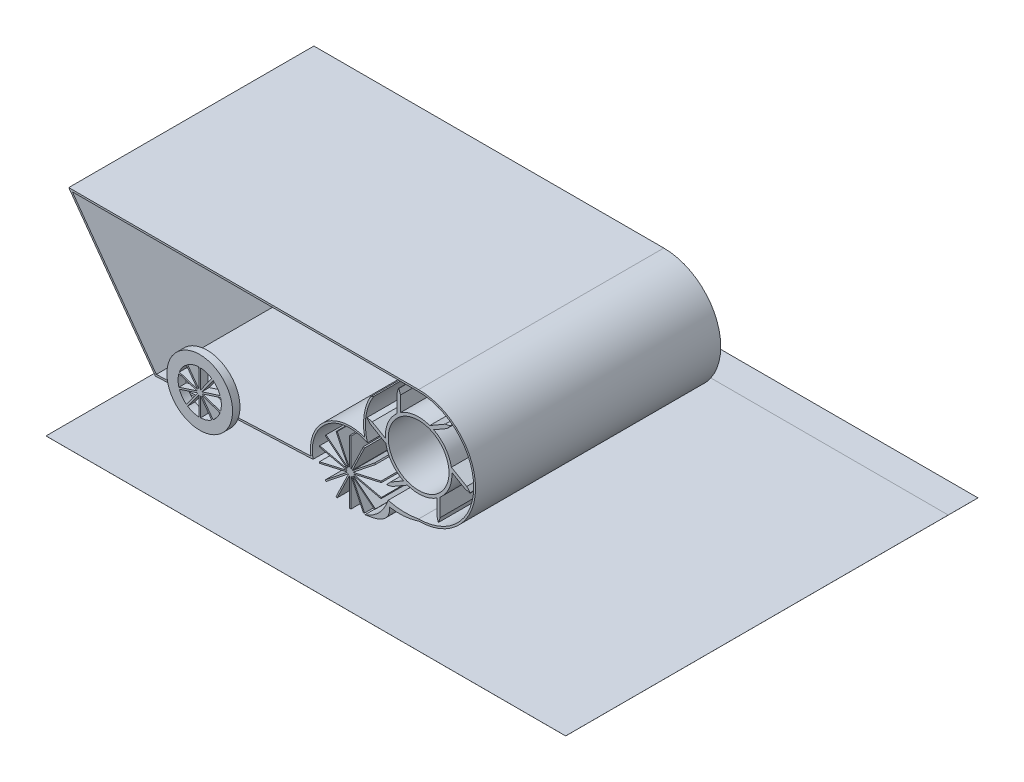
SolidWorks part; units mm, degrees
ref_plane "Front Plane" through (0, 0, 0) normal (0, 0, 1) x (1, 0, 0)
ref_plane "Top Plane" through (0, 0, 0) normal (0, 1, 0) x (1, 0, 0)
ref_plane "Right Plane" through (0, 0, 0) normal (1, 0, 0) x (0, 0, -1)
sketch "Sketch1" plane through (0, 0, 0) normal (0, 0, 1) x (1, 0, 0)
  line L0 (-32.4096, 6.9538) -> (-74.0166, 5.1847)
  line L1 (-79.7094, 0) -> (60.1844, 0)
  line L2 (-79.7094, 0) -> (-79.7094, -0.01)
  line L3 (-79.7094, -0.01) -> (60.1844, -0.01)
  line L4 (60.1844, 0) -> (60.1844, -0.01)
  line L5 (-74.0166, 5.1847) -> (-96.613, 36.459)
  line L6 (-96.613, 36.459) -> (-3.402, 36.459)
  line L7 (-17.8302, 0.5667) -> (-11.617, 7.0387) construction
  line L8 (-17.4695, 0.2204) -> (-11.4099, 6.5323) construction
  line L9 (-31.8198, 6.4784) -> (-74.2642, 4.6737)
  line L10 (-74.2642, 4.6737) -> (-97.5911, 36.959)
  line L11 (-97.5911, 36.959) -> (-3.402, 36.959)
  line L12 (-16.3995, 28.7718) -> (-15.5246, 29.2718)
  line L13 (-11.617, 7.0387) -> (-3.402, 6.7959) construction
  line L14 (-16.3995, 28.7718) -> (-64.1017, 28.7718) construction
  line L15 (-15.5246, 29.2718) -> (-64.1017, 29.2718) construction
  line L16 (-11.4099, 6.5323) -> (-3.4095, 6.2959) construction
  circle A0 centre (-21.7751, 8.5048) radius 8.5048
  circle A1 centre (-3.402, 21.6275) radius 14
  arc A2 (-3.402, 6.7959) -> (-3.402, 36.459) centre (-3.402, 21.6275) ccw
  arc A3 (-17.9069, 18.5316) -> (-32.4096, 6.9538) centre (-21.7751, 8.5048) ccw
  arc A4 (-16.3995, 28.7718) -> (-17.9069, 18.5316) centre (-3.402, 21.6275) ccw
  arc A5 (-15.5246, 29.2718) -> (-17.1737, 17.6606) centre (-3.402, 21.6275) ccw
  arc A6 (-17.1737, 17.6606) -> (-31.8198, 6.4784) centre (-21.7751, 8.5048) ccw
  arc A7 (-3.4095, 6.2959) -> (-3.402, 36.959) centre (-3.402, 21.6275) ccw
  spline S0 degree 2 poles (-17.8302, 0.5667) (-13.2891, 2.1793) (-11.617, 7.0387) knots 0 0 0 1 1 1
  spline S1 degree 2 poles (-11.617, 7.0387) (-7.5737, 5.9985) (-3.402, 6.7959) knots 0 0 0 1 1 1
  spline S2 degree 2 poles (-11.2502, 5.6568) (-7.3029, 4.9959) (-3.4095, 6.2959) knots 0 0 0 1 1 1
  spline S3 degree 3 poles (-17.8302, 0.5667) (-13.1441, 1.0958) (-10.9508, 2.7924) (-11.2502, 5.6568) knots 0 0 0 0 0.910766 0.910766 0.910766 0.910766
  point P15 (-32.4096, 6.9538)
  dimension "D2" = 28
  dimension "D1" = 0.5
extrude "Boss-Extrude1" add sketch "Sketch1" along normal blind 65 contours S0 S3 S2 A7 L11 L10 L9 A6 A5 L12 A4 A3 L0 L5 L6 A2 S1 | A0 | A1 | L1 L4 L3 L2 region at (-28.4081, 16.8136, 0) region at (-21.7751, 8.5048, 0) region at (-3.402, 21.6275, 0)
sketch "Sketch2" plane through (0, 0, 65) normal (0, 0, 1) x (1, 0, 0)
  line L0 (-60.1133, 9.377) -> (-60.1133, 14.6669)
  line L1 (-60.5412, 9.4992) -> (-60.5412, 14.6669)
  line L2 (-60.1133, 9.4992) -> (-57.0757, 13.68)
  line L3 (-59.7671, 9.2476) -> (-56.7295, 13.4285)
  line L4 (-59.7671, 9.2476) -> (-54.8522, 10.8446)
  line L5 (-59.6348, 8.8406) -> (-54.72, 10.4376)
  line L6 (-59.6348, 8.8406) -> (-54.72, 7.2437)
  line L7 (-59.7671, 8.4337) -> (-54.8522, 6.8367)
  line L8 (-59.7671, 8.4337) -> (-56.7295, 4.2528)
  line L9 (-60.1133, 8.1821) -> (-57.0757, 4.0013)
  line L10 (-60.1133, 8.1821) -> (-60.1133, 3.0143)
  line L11 (-60.5412, 8.1821) -> (-60.5412, 3.0143)
  line L12 (-60.5412, 8.1821) -> (-63.5787, 4.0013)
  line L13 (-60.8874, 8.4337) -> (-63.925, 4.2528)
  line L14 (-60.8874, 8.4337) -> (-65.8023, 6.8367)
  line L15 (-61.0196, 8.8406) -> (-65.9345, 7.2437)
  line L16 (-61.0196, 8.8406) -> (-65.9345, 10.4376)
  line L17 (-60.8874, 9.2476) -> (-65.8023, 10.8446)
  line L18 (-60.8874, 9.2476) -> (-63.925, 13.4285)
  line L19 (-60.5412, 9.4992) -> (-63.5787, 13.68)
  circle A0 centre (-60.3272, 8.8406) radius 8.8406
  arc A1 (-60.5412, 14.6669) -> (-63.5787, 13.68) centre (-60.3272, 8.8406) ccw
  circle A2 centre (-60.3272, 8.8406) radius 0.5775
  arc A3 (-63.925, 13.4285) -> (-65.8023, 10.8446) centre (-60.3272, 8.8406) ccw
  arc A4 (-57.0757, 13.68) -> (-60.1133, 14.6669) centre (-60.3272, 8.8406) ccw
  arc A5 (-54.8522, 10.8446) -> (-56.7295, 13.4285) centre (-60.3272, 8.8406) ccw
  arc A6 (-54.72, 7.2437) -> (-54.72, 10.4376) centre (-60.3272, 8.8406) ccw
  arc A7 (-56.7295, 4.2528) -> (-54.8522, 6.8367) centre (-60.3272, 8.8406) ccw
  arc A8 (-60.1133, 3.0143) -> (-57.0757, 4.0013) centre (-60.3272, 8.8406) ccw
  arc A9 (-63.5787, 4.0013) -> (-60.5412, 3.0143) centre (-60.3272, 8.8406) ccw
  arc A10 (-65.8023, 6.8367) -> (-63.925, 4.2528) centre (-60.3272, 8.8406) ccw
  arc A11 (-65.9345, 10.4376) -> (-65.9345, 7.2437) centre (-60.3272, 8.8406) ccw
  point P46 (-60.3272, 8.8406)
  dimension "D1" = 10
extrude "Boss-Extrude2" add sketch "Sketch2" along normal blind 2 contours A0 A11 L16 L15 A10 L14 L13 A9 L12 L11 A8 L10 L9 A7 L8 L7 A6 L6 L5 A5 L4 L3 A4 L2 A2 L0 A3 L18 L17 A1 L1 L19 | A2 region at (-60.3272, 8.8406, 65) region at (-68.9178, 8.8406, 65)
sketch "Sketch3" plane through (0, 0, 0) normal (0, 0, -1) x (-1, 0, 0)
  line L0 (74.2642, 4.6737) -> (97.5911, 36.959) construction
  line L3 (97.5911, 36.959) -> (3.402, 36.959) construction
  line L4 (74.2642, 4.6737) -> (97.5911, 36.959)
  line L7 (97.5911, 36.959) -> (3.402, 36.959)
  line L8 (74.2642, 4.6737) -> (31.8198, 6.4784)
  arc A2 (3.402, 36.959) -> (3.4095, 6.2959) centre (3.402, 21.6275) ccw construction
  arc A3 (31.8198, 6.4784) -> (17.1737, 17.6606) centre (21.7751, 8.5048) ccw construction
  arc A5 (3.402, 36.959) -> (3.4095, 6.2959) centre (3.402, 21.6275) ccw
  arc A6 (10.9101, 9.42) -> (17.1737, 17.6606) centre (3.402, 21.6275) ccw
  arc A7 (10.9101, 9.42) -> (11.2502, 5.6568) centre (21.7751, 8.5048) ccw
  arc A8 (31.8198, 6.4784) -> (17.1737, 17.6606) centre (21.7751, 8.5048) ccw
  parabola Q0 (11.2502, 5.6568) -> (3.4095, 6.2959) focus (8.3793, 13.3008) apex (8.1633, 5.44) construction
  parabola Q1 (11.2502, 5.6568) -> (3.4095, 6.2959) focus (8.3793, 13.3008) apex (8.1633, 5.44)
extrude "Boss-Extrude4" add sketch "Sketch3" along normal blind 1
pattern_linear "LPattern2" count 2 spacing 68 along (0, 0, -1) of "Boss-Extrude2"
sketch "Sketch4" plane through (0, 0, 65) normal (0, 0, 1) x (1, 0, 0)
  line L0 (-8.2948, 24.7697) -> (-8.2948, 33.2338)
  line L1 (-9.2169, 21.6275) -> (-9.2169, 33.2338)
  line L2 (-9.2169, 33.2338) -> (-8.7548, 34.7598)
  line L3 (-8.7548, 34.7598) -> (-8.2948, 33.2338)
  line L4 (-6.3095, 26.6633) -> (3.7419, 32.4665)
  line L5 (-3.1272, 27.4359) -> (4.203, 31.6679)
  line L6 (3.7419, 32.4665) -> (5.2946, 32.8293)
  line L7 (5.2946, 32.8293) -> (4.203, 31.6679)
  line L8 (-0.4946, 26.6633) -> (9.5568, 20.8601)
  line L9 (1.7656, 24.2937) -> (9.0958, 20.0616)
  line L10 (9.5568, 20.8601) -> (10.6474, 19.6969)
  line L11 (10.6474, 19.6969) -> (9.0958, 20.0616)
  line L12 (2.4129, 21.6275) -> (2.4129, 10.0211)
  line L13 (1.4908, 18.4852) -> (1.4908, 10.0211)
  line L14 (2.4129, 10.0211) -> (1.9508, 8.4951)
  line L15 (1.9508, 8.4951) -> (1.4908, 10.0211)
  line L16 (-0.4946, 16.5916) -> (-10.546, 10.7884)
  line L17 (-3.6768, 15.819) -> (-11.007, 11.587)
  line L18 (-10.546, 10.7884) -> (-12.0986, 10.4256)
  line L19 (-12.0986, 10.4256) -> (-11.007, 11.587)
  line L20 (-6.3095, 16.5916) -> (-16.3609, 22.3948)
  line L21 (-8.5697, 18.9613) -> (-15.8998, 23.1933)
  line L22 (-16.3609, 22.3948) -> (-17.4514, 23.558)
  line L23 (-17.4514, 23.558) -> (-15.8998, 23.1933)
  circle A0 centre (-3.402, 21.6275) radius 14 construction
  circle A1 centre (-3.402, 21.6275) radius 14
  arc A2 (-6.3095, 16.5916) -> (-3.6768, 15.819) centre (-3.402, 21.6275) ccw
  arc A3 (-9.2169, 21.6275) -> (-8.5697, 18.9613) centre (-3.402, 21.6275) ccw
  arc A4 (-6.3095, 26.6633) -> (-8.2948, 24.7697) centre (-3.402, 21.6275) ccw
  arc A5 (-0.4946, 26.6633) -> (-3.1272, 27.4359) centre (-3.402, 21.6275) ccw
  arc A6 (2.4129, 21.6275) -> (1.7656, 24.2937) centre (-3.402, 21.6275) ccw
  arc A7 (-0.4946, 16.5916) -> (1.4908, 18.4852) centre (-3.402, 21.6275) ccw
  point P36 (-3.402, 21.6275)
  circle M3 centre (-3.402, 21.6275) radius 14
  dimension "D1" = 0.46
  dimension "D4" = 28
  dimension "D2" = 0.9221
  dimension "D3" = 6
extrude "Cut-Extrude1" cut sketch "Sketch4" against normal blind 65 contours A3 L1 L2 L23 L21 M3 | A4 L4 L6 L3 L0 M3 | A5 L8 L10 L7 L5 M3 | A6 L12 L14 L11 L9 M3 | A7 L16 L18 L15 L13 M3 | A2 L20 L22 L19 L17 M3 region at (-3.5403, 31.7426, 65) region at (-12.2311, 26.5653, 65) region at (5.2889, 26.8048, 65) region at (-12.0929, 16.4501, 65) region at (5.4271, 16.6896, 65) region at (-3.2638, 11.5123, 65)
sketch "Sketch5" plane through (0, 0, 65) normal (0, 0, 1) x (1, 0, 0)
  line L0 (-21.6021, 9.4365) -> (-21.6021, 17.0079)
  line L1 (-21.9481, 9.4365) -> (-21.9481, 17.0079)
  line L2 (-21.9481, 17.0079) -> (-21.8647, 16.5246)
  line L3 (-21.8647, 16.5246) -> (-21.7751, 17.0097)
  line L4 (-21.7751, 17.0097) -> (-21.6914, 16.5246)
  line L5 (-21.6914, 16.5246) -> (-21.6021, 17.0079)
  line L6 (-21.5267, 9.4193) -> (-18.2416, 16.2409)
  line L7 (-21.215, 9.2692) -> (-17.9299, 16.0908)
  line L8 (-18.2416, 16.2409) -> (-18.3762, 15.7692)
  line L9 (-18.3762, 15.7692) -> (-18.085, 16.1674)
  line L10 (-18.085, 16.1674) -> (-18.2201, 15.6941)
  line L11 (-18.2201, 15.6941) -> (-17.9299, 16.0908)
  line L12 (-21.1546, 9.2209) -> (-15.235, 13.9417)
  line L13 (-20.9389, 8.9505) -> (-15.0193, 13.6712)
  line L14 (-15.235, 13.9417) -> (-15.5609, 13.5751)
  line L15 (-15.5609, 13.5751) -> (-15.1258, 13.8075)
  line L16 (-15.1258, 13.8075) -> (-15.4529, 13.4396)
  line L17 (-15.4529, 13.4396) -> (-15.0193, 13.6712)
  line L18 (-20.9053, 8.8808) -> (-13.5237, 10.5656)
  line L19 (-20.8283, 8.5435) -> (-13.4467, 10.2283)
  line L20 (-13.5237, 10.5656) -> (-13.9764, 10.3768)
  line L21 (-13.9764, 10.3768) -> (-13.4835, 10.3973)
  line L22 (-13.4835, 10.3973) -> (-13.9378, 10.2078)
  line L23 (-13.9378, 10.2078) -> (-13.4467, 10.2283)
  line L24 (-20.8283, 8.4662) -> (-13.4467, 6.7814)
  line L25 (-20.9053, 8.1289) -> (-13.5237, 6.4441)
  line L26 (-13.4467, 6.7814) -> (-13.9365, 6.8077)
  line L27 (-13.9365, 6.8077) -> (-13.4835, 6.6123)
  line L28 (-13.4835, 6.6123) -> (-13.9751, 6.6387)
  line L29 (-13.9751, 6.6387) -> (-13.5237, 6.4441)
  line L30 (-20.9389, 8.0592) -> (-15.0193, 3.3385)
  line L31 (-21.1546, 7.7887) -> (-15.235, 3.068)
  line L32 (-15.0193, 3.3385) -> (-15.4492, 3.5747)
  line L33 (-15.4492, 3.5747) -> (-15.1258, 3.2022)
  line L34 (-15.1258, 3.2022) -> (-15.5572, 3.4392)
  line L35 (-15.5572, 3.4392) -> (-15.235, 3.068)
  line L36 (-21.215, 7.7405) -> (-17.9299, 0.9189)
  line L37 (-21.5267, 7.5904) -> (-18.2416, 0.7688)
  line L38 (-17.9299, 0.9189) -> (-18.2147, 1.3182)
  line L39 (-18.2147, 1.3182) -> (-18.085, 0.8422)
  line L40 (-18.085, 0.8422) -> (-18.3709, 1.243)
  line L41 (-18.3709, 1.243) -> (-18.2416, 0.7688)
  line L42 (-21.6021, 7.5732) -> (-21.6021, 0.0018)
  line L43 (-21.9481, 7.5732) -> (-21.9481, 0.0018)
  line L44 (-21.6021, 0.0018) -> (-21.6855, 0.4851)
  line L45 (-21.6855, 0.4851) -> (-21.7751, 0)
  line L46 (-21.7751, 0) -> (-21.8588, 0.4851)
  line L47 (-21.8588, 0.4851) -> (-21.9481, 0.0018)
  line L48 (-22.0235, 7.5904) -> (-25.3086, 0.7688)
  line L49 (-22.3352, 7.7405) -> (-25.6203, 0.9189)
  line L50 (-25.3086, 0.7688) -> (-25.174, 1.2404)
  line L51 (-25.174, 1.2404) -> (-25.4652, 0.8422)
  line L52 (-25.4652, 0.8422) -> (-25.3301, 1.3156)
  line L53 (-25.3301, 1.3156) -> (-25.6203, 0.9189)
  line L54 (-22.3956, 7.7887) -> (-28.3152, 3.068)
  line L55 (-22.6113, 8.0592) -> (-28.5309, 3.3385)
  line L56 (-28.3152, 3.068) -> (-27.9893, 3.4346)
  line L57 (-27.9893, 3.4346) -> (-28.4245, 3.2022)
  line L58 (-28.4245, 3.2022) -> (-28.0974, 3.57)
  line L59 (-28.0974, 3.57) -> (-28.5309, 3.3385)
  line L60 (-22.6449, 8.1289) -> (-30.0265, 6.4441)
  line L61 (-22.7219, 8.4662) -> (-30.1035, 6.7814)
  line L62 (-30.0265, 6.4441) -> (-29.5738, 6.6329)
  line L63 (-29.5738, 6.6329) -> (-30.0667, 6.6123)
  line L64 (-30.0667, 6.6123) -> (-29.6124, 6.8019)
  line L65 (-29.6124, 6.8019) -> (-30.1035, 6.7814)
  line L66 (-22.7219, 8.5435) -> (-30.1035, 10.2283)
  line L67 (-22.6449, 8.8808) -> (-30.0265, 10.5656)
  line L68 (-30.1035, 10.2283) -> (-29.6137, 10.202)
  line L69 (-29.6137, 10.202) -> (-30.0667, 10.3973)
  line L70 (-30.0667, 10.3973) -> (-29.5751, 10.371)
  line L71 (-29.5751, 10.371) -> (-30.0265, 10.5656)
  line L72 (-22.6113, 8.9505) -> (-28.5309, 13.6712)
  line L73 (-22.3956, 9.2209) -> (-28.3152, 13.9417)
  line L74 (-28.5309, 13.6712) -> (-28.1011, 13.435)
  line L75 (-28.1011, 13.435) -> (-28.4245, 13.8075)
  line L76 (-28.4245, 13.8075) -> (-27.993, 13.5705)
  line L77 (-27.993, 13.5705) -> (-28.3152, 13.9417)
  line L78 (-22.3352, 9.2692) -> (-25.6203, 16.0908)
  line L79 (-22.0235, 9.4193) -> (-25.3086, 16.2409)
  line L80 (-25.6203, 16.0908) -> (-25.3355, 15.6915)
  line L81 (-25.3355, 15.6915) -> (-25.4652, 16.1674)
  line L82 (-25.4652, 16.1674) -> (-25.1794, 15.7667)
  line L83 (-25.1794, 15.7667) -> (-25.3086, 16.2409)
  arc A16 (-20.9389, 8.0592) -> (-20.9053, 8.1289) centre (-21.7751, 8.5048) ccw
  circle A17 centre (-21.7751, 8.5048) radius 8.5048 construction
  circle A18 centre (-21.7751, 8.5048) radius 8.5048
  arc A19 (-21.215, 7.7405) -> (-21.1546, 7.7887) centre (-21.7751, 8.5048) ccw
  arc A20 (-21.6021, 7.5732) -> (-21.5267, 7.5904) centre (-21.7751, 8.5048) ccw
  arc A21 (-22.0235, 7.5904) -> (-21.9481, 7.5732) centre (-21.7751, 8.5048) ccw
  arc A22 (-22.3956, 7.7887) -> (-22.3352, 7.7405) centre (-21.7751, 8.5048) ccw
  arc A23 (-22.6449, 8.1289) -> (-22.6113, 8.0592) centre (-21.7751, 8.5048) ccw
  arc A24 (-22.7219, 8.5435) -> (-22.7219, 8.4662) centre (-21.7751, 8.5048) ccw
  arc A25 (-22.6113, 8.9505) -> (-22.6449, 8.8808) centre (-21.7751, 8.5048) ccw
  arc A26 (-22.3352, 9.2692) -> (-22.3956, 9.2209) centre (-21.7751, 8.5048) ccw
  arc A27 (-21.9481, 9.4365) -> (-22.0235, 9.4193) centre (-21.7751, 8.5048) ccw
  arc A28 (-21.5267, 9.4193) -> (-21.6021, 9.4365) centre (-21.7751, 8.5048) ccw
  arc A29 (-20.9053, 8.8808) -> (-20.9389, 8.9505) centre (-21.7751, 8.5048) ccw
  arc A30 (-20.8283, 8.4662) -> (-20.8283, 8.5435) centre (-21.7751, 8.5048) ccw
  arc A31 (-21.1546, 9.2209) -> (-21.215, 9.2692) centre (-21.7751, 8.5048) ccw
  point P104 (-21.7751, 8.5048)
  circle M85 centre (-21.7751, 8.5048) radius 8.5048
  dimension "D1" = 14
extrude "Cut-Extrude7" cut sketch "Sketch5" against normal blind 65 contours A26 L78 L73 M85 | A27 L1 L79 M85 | A28 L6 L0 M85 | A31 L12 L7 M85 | A29 L18 L13 M85 | A30 L24 L19 M85 | A16 L30 L25 M85 | A19 L36 L31 M85 | A20 L42 L37 M85 | A21 L48 L43 M85 | A22 L54 L49 M85 | A23 L60 L55 M85 | A24 L66 L61 M85 | A25 L72 L67 M85 region at (-20.464, 14.2493, 65) region at (-23.0862, 14.2493, 65) region at (-18.1014, 13.1115, 65) region at (-25.4488, 13.1115, 65) region at (-16.4664, 11.0614, 65) region at (-27.0838, 11.0614, 65) region at (-15.8829, 8.5048, 65) region at (-27.6673, 8.5048, 65) region at (-16.4664, 5.9483, 65) region at (-27.0838, 5.9483, 65) region at (-18.1014, 3.8981, 65) region at (-25.4488, 3.8981, 65) region at (-20.464, 2.7604, 65) region at (-23.0862, 2.7604, 65)
sketch "Sketch7" plane through (0, 0, 65) normal (0, 0, 1) x (1, 0, 0)
  line L1 (-79.7094, 0) -> (60.1844, 0)
  line L2 (-79.7094, 0) -> (-79.7094, -0.01)
  line L3 (-79.7094, -0.01) -> (60.1844, -0.01)
  line L4 (60.1844, 0) -> (60.1844, -0.01)
extrude "Boss-Extrude5" add sketch "Sketch7" along normal blind 24 and the other way blind 79
sketch "Sketch8" plane through (0, 0, 65) normal (0, 0, 1) x (1, 0, 0)
  circle A13 centre (-3.402, 21.6275) radius 8.9663
extrude "Boss-Extrude6" add sketch "Sketch8" against normal blind 65
sketch "Sketch9" plane through (0, 0, 65) normal (0, 0, 1) x (1, 0, 0)
  circle A2 centre (-3.402, 21.6275) radius 8.1744
extrude "Cut-Extrude8" cut sketch "Sketch9" against normal blind 65
sketch "Sketch10" plane through (0, 0, 65) normal (0, 0, 1) x (1, 0, 0)
  circle A0 centre (-13.2688, 2.0846) radius 2.0846
extrude "Boss-Extrude7" [suppressed] add sketch "Sketch10" along normal blind 2
pattern_linear "LPattern3" [suppressed] count 2 spacing 67 of bodies 130
sketch "Sketch11" plane through (0, 0, 65) normal (0, 0, 1) x (1, 0, 0)
  line L0 (-16.3995, 28.7718) -> (-39.2517, 6.6629)
  line L1 (-32.4096, 6.9538) -> (-74.0166, 5.1847) construction
  line L2 (-32.4096, 6.9538) -> (-51.9142, 6.1245) construction
  line L3 (-32.4096, 6.9538) -> (-39.2517, 6.6629)
  arc A0 (-17.9069, 18.5316) -> (-32.4096, 6.9538) centre (-21.7751, 8.5048) ccw construction
  arc A1 (-16.3995, 28.7718) -> (-17.9069, 18.5316) centre (-3.402, 21.6275) ccw construction
  arc A2 (-17.9069, 18.5316) -> (-32.4096, 6.9538) centre (-21.7751, 8.5048) ccw
  arc A3 (-16.3995, 28.7718) -> (-17.9069, 18.5316) centre (-3.402, 21.6275) ccw
extrude "Boss-Extrude8" [suppressed] add sketch "Sketch11" against normal blind 65
extrude "Boss-Extrude9" add sketch "Sketch1<3>" along normal blind 69 and the other way blind 22 separate body contours L4 L1 L2 L3 region at (-9.7625, -0.005, 0)
sketch "Sketch1<3>" plane through (0, 0, 0) normal (0, 0, 1) x (1, 0, 0) same geometry as "Sketch1"
sketch "Sketch12" plane through (0, 0, 0) normal (0, 0, 1) x (1, 0, 0)
  circle A0 centre (-3.402, 21.6275) radius 14.3316
